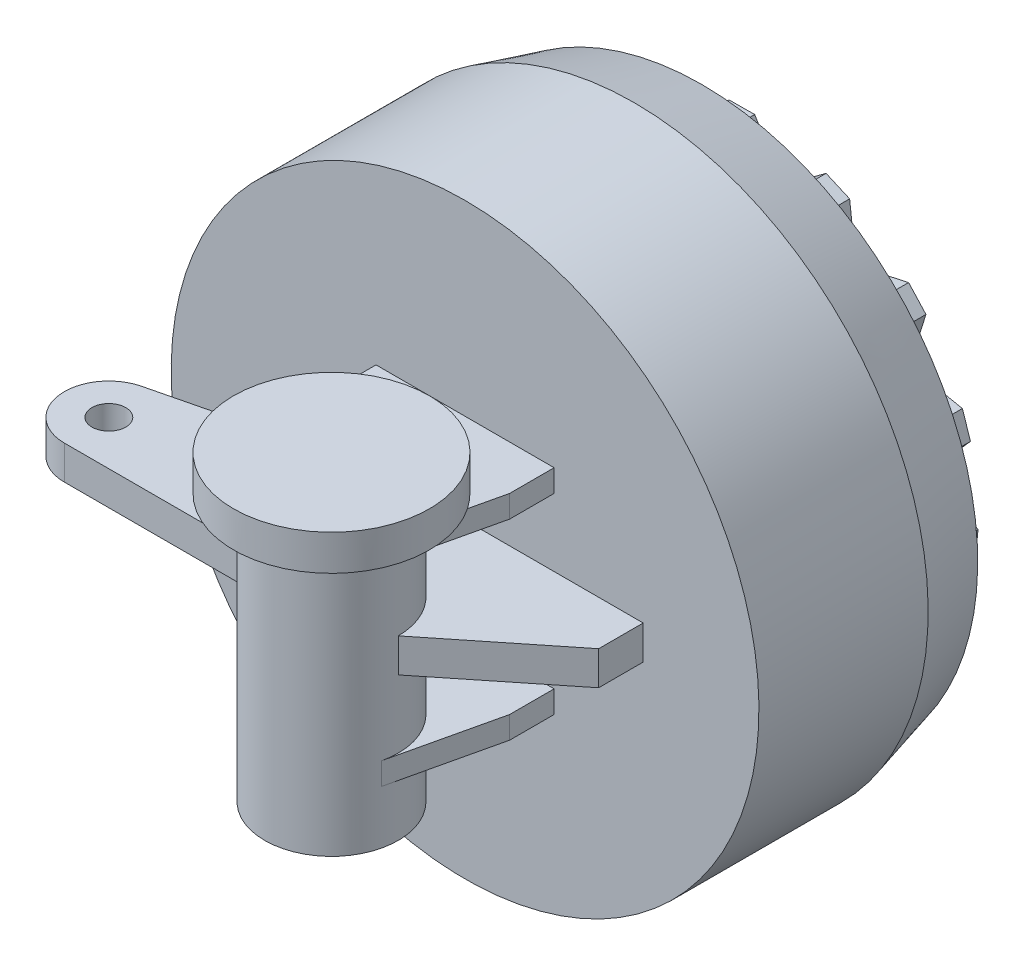
SolidWorks part; units mm, degrees
ref_plane "Front Plane" through (0, 0, 0) normal (0, 0, 1) x (1, 0, 0)
ref_plane "Top Plane" through (0, 0, 0) normal (0, 1, 0) x (1, 0, 0)
ref_plane "Right Plane" through (0, 0, 0) normal (1, 0, 0) x (0, 0, -1)
sketch "Sketch2" plane through (0, 0, 0) normal (1, 0, 0) x (0, 0, -1)
  line L0 (0, 0) -> (0, 165)
  line L1 (0, 165) -> (95, 165)
  line L2 (95, 165) -> (133, 154.8179)
  line L3 (133, 154.8179) -> (133, 75)
  line L4 (133, 75) -> (158, 75)
  line L5 (158, 75) -> (158, 50)
  line L6 (158, 50) -> (183, 50)
  line L7 (183, 50) -> (183, 0)
  line L8 (183, 0) -> (0, 0)
  point P12 (142.3145, 131.7921)
  dimension "D1" = 165
  dimension "D2" = 95
  dimension "D3" = 38
  dimension "D4" = 15
  dimension "D5" = 25
  dimension "D6" = 25
  dimension "D7" = 50
  dimension "D8" = 25
revolve "Revolve1" add sketch "Sketch2" angle 360 about L8
chamfer "Chamfer1" distance 4 angle 45 1 edges at (0, 50, -183)
fillet "Fillet1" radius 3.5 2 edges at (0, 75, -158) (0, 50, -158)
sketch "Sketch3" plane through (0, 0, 0) normal (0, 1, 0) x (1, 0, 0)
  circle A0 centre (0, -75) radius 37.5
  point P2 (0, 0)
  point P4 (0, 0)
  dimension "D1" = 75
  dimension "D2" = 75
extrude "Boss-Extrude1" add sketch "Sketch3" against normal blind 90 and the other way blind 80 separate body
sketch "Sketch4" plane through (0, 0, 0) normal (0, 1, 0) x (1, 0, 0)
  line L0 (36.543, -83.418) -> (50, -25)
  line L1 (50, -25) -> (50, 0)
  line L2 (-165, 0) -> (165, 0) construction
  line L3 (50, 0) -> (-50, 0)
  line L4 (0, 0) -> (0, -139.3249) construction
  line L5 (-50, -25) -> (-50, 0)
  line L6 (-36.543, -83.418) -> (-50, -25)
  line L7 (-36.543, -83.418) -> (36.543, -83.418)
  circle A0 centre (0, -75) radius 37.5 construction
  dimension "D1" = 25
  dimension "D2" = 50
extrude "Boss-Extrude2" add sketch "Sketch4" against normal blind 12.5 from offset 60 separate body
mirror "Mirror2" about plane through (0, 0, 0) normal (0, 1, 0) of "Boss-Extrude2"
sketch "Sketch5" plane through (0, 0, 0) normal (0, 1, 0) x (1, 0, 0)
  line L0 (-50, 0) -> (100, 0)
  line L1 (-165, 0) -> (165, 0) construction
  line L2 (100, 0) -> (100, -25)
  line L3 (100, -25) -> (37.5, -75)
  line L4 (-37.5, -75) -> (-150, -75)
  line L5 (-155.8972, -25.7055) -> (-50, 0)
  line L6 (-50, 0) -> (100, 0)
  line L7 (0, -75) -> (-75, -75) construction
  line L8 (-75, -75) -> (123.78, -75) construction
  arc A1 (-150, -75) -> (-155.8972, -25.7055) centre (-150, -50) cw
  circle A2 centre (0, -75) radius 37.5 construction
  arc A3 (37.5, -75) -> (-37.5, -75) centre (0, -75) ccw
  arc A4 (36.543, -83.418) -> (-36.543, -83.418) centre (0, -75) ccw construction
  arc A5 (-37.5, -75) -> (37.5, -75) centre (0, -75) cw
  circle A6 centre (-150, -50) radius 9.5
  dimension "D3" = 25
  dimension "D6" = 19
  dimension "D1" = 25
  dimension "D2" = 150
  dimension "D4" = 100
  dimension "D5" = 150
extrude "Boss-Extrude3" add sketch "Sketch5" along normal mid plane 19 contours A3 L3 L2 L0 L5 A1 L4 A6 region at (-39.1452, 0, 35.023)
sketch "Sketch6" plane through (0, 60, 0) normal (0, 1, 0) x (1, 0, 0)
  circle A0 centre (0, -75) radius 55
  dimension "D1" = 110
extrude "Boss-Extrude4" add sketch "Sketch6" along normal up to surface (20 mm away) up to face at (0, 80, 112.5)
sketch "Sketch7" plane through (0, 0, -133) normal (0, 0, -1) x (-1, 0, 0)
  line L1 (-7.1226, 132.5539) -> (-14.4333, 120.1086)
  line L2 (-14.4333, 120.1086) -> (-7.3107, 107.5546)
  line L3 (-7.3107, 107.5546) -> (7.1226, 107.4461)
  line L4 (7.1226, 107.4461) -> (14.4333, 119.8914)
  line L5 (14.4333, 119.8914) -> (7.3107, 132.4454)
  line L6 (7.3107, 132.4454) -> (-7.1226, 132.5539)
  circle A0 centre (0, 120) radius 12.5 construction
  circle A1 centre (0, 120) radius 7.5
  dimension "D2" = 15
  dimension "D1" = 25
  dimension "D3" = 120
extrude "Boss-Extrude5" add sketch "Sketch7" along normal blind 25 contours A1 region at (0, 120, -133)
extrude "Boss-Extrude6" add sketch "Sketch7<3>" along normal blind 12.5 from offset 10
sketch "Sketch7<3>" plane through (0, 0, -133) normal (0, 0, -1) x (-1, 0, 0) same geometry as "Sketch7"
pattern_circular "CirPattern1" count 15 every 24 about axis through (0, 0, -183) along (0, 0, -1) of "Boss-Extrude6", "Boss-Extrude5"
